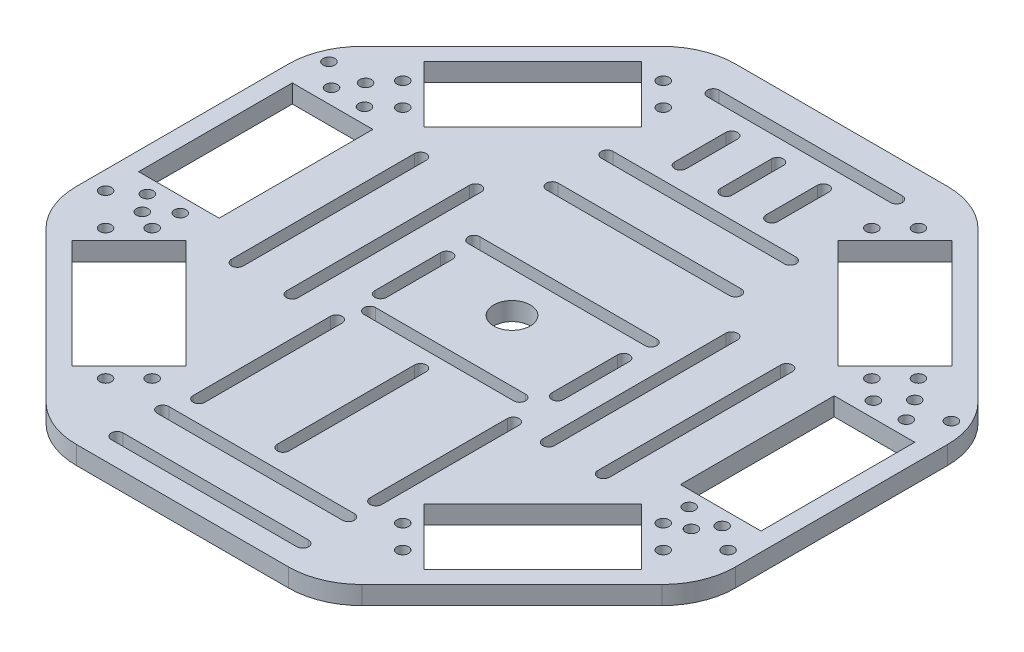
SolidWorks part; units mm, degrees
ref_plane "Front Plane" through (0, 0, 0) normal (0, 0, 1) x (1, 0, 0)
ref_plane "Top Plane" through (0, 0, 0) normal (0, 1, 0) x (1, 0, 0)
ref_plane "Right Plane" through (0, 0, 0) normal (1, 0, 0) x (0, 0, -1)
sketch "Sketch1" plane through (0, 0, 0) normal (0, 1, 0) x (1, 0, 0)
  line L1 (-90, -37.2792) -> (-37.2792, -90)
  line L2 (-37.2792, -90) -> (37.2792, -90)
  line L3 (37.2792, -90) -> (90, -37.2792)
  line L4 (90, -37.2792) -> (90, 37.2792)
  line L5 (90, 37.2792) -> (37.2792, 90)
  line L6 (37.2792, 90) -> (-37.2792, 90)
  line L7 (-37.2792, 90) -> (-90, 37.2792)
  line L8 (-90, 37.2792) -> (-90, -37.2792)
  line L12 (63.6396, -63.6396) -> (0, 0) construction
  line L21 (-20.4, -34.5422) -> (-34.5422, -20.4)
  line L22 (-20.4, -34.5422) -> (-50.0985, -64.2407)
  line L23 (-50.0985, -64.2407) -> (-64.2407, -50.0985)
  line L24 (-34.5422, -20.4) -> (-64.2407, -50.0985)
  line L25 (-38.85, -10) -> (-38.85, 10)
  line L26 (-38.85, -10) -> (-80.85, -10)
  line L27 (-80.85, -10) -> (-80.85, 10)
  line L28 (-38.85, 10) -> (-80.85, 10)
  line L29 (-34.5422, 20.4) -> (-20.4, 34.5422)
  line L30 (-34.5422, 20.4) -> (-64.2407, 50.0985)
  line L31 (-64.2407, 50.0985) -> (-50.0985, 64.2407)
  line L32 (-20.4, 34.5422) -> (-50.0985, 64.2407)
  line L37 (20.4, 34.5422) -> (34.5422, 20.4)
  line L38 (20.4, 34.5422) -> (50.0985, 64.2407)
  line L39 (50.0985, 64.2407) -> (64.2407, 50.0985)
  line L40 (34.5422, 20.4) -> (64.2407, 50.0985)
  line L41 (38.85, 10) -> (38.85, -10)
  line L42 (38.85, 10) -> (80.85, 10)
  line L43 (80.85, 10) -> (80.85, -10)
  line L44 (38.85, -10) -> (80.85, -10)
  circle A0 centre (0, 0) radius 90 construction
  circle A13 centre (0, 0) radius 90 construction
  circle A14 centre (-27.7186, -21.3546) radius 2.5
  circle A15 centre (-21.3546, -27.7186) radius 2.5
  circle A16 centre (-56.9221, -63.2861) radius 2.5
  circle A17 centre (-63.2861, -56.9221) radius 2.5
  circle A18 centre (0, 0) radius 90 construction
  circle A19 centre (-34.7, 4.5) radius 2.5
  circle A20 centre (-34.7, -4.5) radius 2.5
  circle A21 centre (-85, -4.5) radius 2.5
  circle A22 centre (-85, 4.5) radius 2.5
  circle A23 centre (0, 0) radius 90 construction
  circle A24 centre (-21.3546, 27.7186) radius 2.5
  circle A25 centre (-27.7186, 21.3546) radius 2.5
  circle A26 centre (-63.2861, 56.9221) radius 2.5
  circle A27 centre (-56.9221, 63.2861) radius 2.5
  circle A28 centre (0, 0) radius 90 construction
  circle A33 centre (0, 0) radius 90 construction
  circle A34 centre (27.7186, 21.3546) radius 2.5
  circle A35 centre (21.3546, 27.7186) radius 2.5
  circle A36 centre (56.9221, 63.2861) radius 2.5
  circle A37 centre (63.2861, 56.9221) radius 2.5
  circle A38 centre (0, 0) radius 90 construction
  circle A39 centre (34.7, -4.5) radius 2.5
  circle A40 centre (34.7, 4.5) radius 2.5
  circle A41 centre (85, 4.5) radius 2.5
  circle A42 centre (85, -4.5) radius 2.5
  circle A43 centre (0, 0) radius 90 construction
  point P15 (63.6396, -63.6396)
  point P16 (60.1041, -60.1041)
  point P17 (57.1696, -57.1696)
  point P121 (0, 0)
  dimension "D1" = 90
  dimension "D12" = 8
extrude "Baseplate" add sketch "Sketch1" along normal blind 5 contours L7 L8 L1 L2 L3 L4 L5 L6 A42 A41 A40 A39 A37 A36 A35 A34 A27 A26 A25 A24 A22 A21 A20 A19 A17 A16 A15 A14 L44 L41 | L29 L32 L31 L30 | L37 L40 L39 L38 | L41 L44 L43 L42 | L25 L28 L27 L26 | A27 | A26 | A25 | A24 | A22 | A21 | A19 | A20 | A14 | A15 | A17 | A16 | A40 | A41 | A42 | A35 | A34 | A39 | A37 | A36 | L21 L24 L23 L22 region at (1.7472, 0, 1.7472) region at (-59.85, 0, 0) region at (-42.3203, 0, -42.3203) region at (42.3203, 0, -42.3203) region at (59.85, 0, 0) region at (-27.7186, 0, 21.3546) region at (-21.3546, 0, 27.7186) region at (-56.9221, 0, 63.2861) region at (-63.2861, 0, 56.9221) region at (-34.7, 0, -4.5) region at (-34.7, 0, 4.5) region at (-85, 0, 4.5) region at (-85, 0, -4.5) region at (-21.3546, 0, -27.7186) region at (-27.7186, 0, -21.3546) region at (-63.2861, 0, -56.9221) region at (-56.9221, 0, -63.2861) region at (34.7, 0, -4.5) region at (85, 0, -4.5) region at (85, 0, 4.5)
fillet "Fillet1" radius 20 8 edges at (-90, 2.5, -37.2792) (-37.2792, 2.5, -90) (37.2792, 2.5, -90) (90, 2.5, -37.2792) (90, 2.5, 37.2792) (37.2792, 2.5, 90) (-37.2792, 2.5, 90) (-90, 2.5, 37.2792)
sketch "Sketch2" plane through (0, 5, 0) normal (0, 1, 0) x (1, 0, 0)
  line L0 (90, -28.9949) -> (90, 28.9949) construction
  line L1 (63, 25.0051) -> (85, 25.0051)
  line L2 (63, 25.0051) -> (63, -16.9949)
  line L3 (63, -16.9949) -> (85, -16.9949)
  line L4 (85, 25.0051) -> (85, -16.9949)
  circle A0 centre (78.5, 29.2051) radius 1.6
  circle A1 centre (69.5, 29.2051) radius 1.6
  circle A2 centre (69.5, -21.0949) radius 1.6
  circle A3 centre (78.5, -21.0949) radius 1.6
  point P8 (74, 25.0051)
  dimension "D1" = 3.2
  dimension "D2" = 9
  dimension "D3" = 50.3
  dimension "D4" = 22
  dimension "D5" = 42
  dimension "D6" = 4.2
  dimension "D7" = 4.5
  dimension "D8" = 5
  dimension "D9" = 12
extrude "Servo hole" cut sketch "Sketch2" against normal through all contours A0 | L4 L1 L2 L3 | A2 | A3 | A1 region at (74, 5, -4.0051) region at (78.5, 5, -29.2051) region at (69.5, 5, 21.0949) region at (78.5, 5, 21.0949)
sketch "Sketch3" plane through (0, 5, 0) normal (0, 1, 0) x (1, 0, 0)
  circle A0 centre (0, 0) radius 5
  dimension "D1" = 10
extrude "Center hole" cut sketch "Sketch3" against normal through all
pattern_circular "Servo hole pattern" count 8 over 360 about axis through (0, 5, 0) along (0, 1, 0) skipping 2, 3, 4, 5, 6 of "Servo hole"
sketch "Sketch4" plane through (0, 5, 0) normal (0, 1, 0) x (1, 0, 0)
  line L0 (-28.9949, -90) -> (28.9949, -90) construction
  line L1 (-90, 28.9949) -> (-90, -28.9949) construction
  circle A0 centre (-23, 5.1332) radius 1.6
  circle A1 centre (-23, -70) radius 1.6
  circle A2 centre (25.3362, 12.6262) radius 1.6
  circle A3 centre (25.3362, -70) radius 1.6
  circle A4 centre (-7.5585, -18.3745) radius 1.6
  circle A5 centre (20.4577, -18.3745) radius 1.6
  dimension "D1" = 3.2
  dimension "D8" = 20
  dimension "D2" = 7.493
  dimension "D3" = 48.3362
  dimension "D4" = 31.0007
  dimension "D5" = 51.6255
  dimension "D6" = 4.8785
  dimension "D7" = 28.0162
  dimension "D9" = 67
extrude "Arduino Screw holes" cut sketch "Sketch4" against normal through all
ref_plane "Midplane" through (0, 0, 0) normal (1, 0, 0) x (0, 0, -1)
mirror "Mirror1" about plane through (0, 0, 0) normal (1, 0, 0) of "Servo hole pattern", "Servo hole"
sketch "Sketch5" plane through (0, 5, 0) normal (0, 1, 0) x (1, 0, 0)
  line L0 (-25, 36) -> (25, 36) construction
  line L1 (-25, 37.6) -> (25, 37.6)
  line L2 (-25, 34.4) -> (25, 34.4)
  line L3 (-25, 51) -> (25, 51) construction
  line L4 (-25, 52.6) -> (25, 52.6)
  line L5 (-25, 49.4) -> (25, 49.4)
  line L6 (-50, 25) -> (-50, -25) construction
  line L7 (-48.4, 25) -> (-48.4, -25)
  line L8 (-51.6, 25) -> (-51.6, -25)
  line L9 (-35, 25) -> (-35, -25) construction
  line L10 (-33.4, 25) -> (-33.4, -25)
  line L11 (-36.6, 25) -> (-36.6, -25)
  line L12 (35, 25) -> (35, -25) construction
  line L13 (36.6, 25) -> (36.6, -25)
  line L14 (33.4, 25) -> (33.4, -25)
  line L15 (50, 25) -> (50, -25) construction
  line L16 (51.6, 25) -> (51.6, -25)
  line L17 (48.4, 25) -> (48.4, -25)
  line L18 (-25, 80) -> (25, 80) construction
  line L19 (-25, 81.6) -> (25, 81.6)
  line L20 (-25, 78.4) -> (25, 78.4)
  line L21 (-12.5, 72.5) -> (-12.5, 58.5) construction
  line L22 (-10.9, 72.5) -> (-10.9, 58.5)
  line L23 (-14.1, 72.5) -> (-14.1, 58.5)
  line L24 (12.5, 72.5) -> (12.5, 58.5) construction
  line L25 (14.1, 72.5) -> (14.1, 58.5)
  line L26 (10.9, 72.5) -> (10.9, 58.5)
  line L27 (28.9949, 90) -> (-28.9949, 90) construction
  line L28 (0, 72.5) -> (0, 58.5) construction
  line L29 (1.6, 72.5) -> (1.6, 58.5)
  line L30 (-1.6, 72.5) -> (-1.6, 58.5)
  arc A0 (-25, 37.6) -> (-25, 34.4) centre (-25, 36) ccw
  arc A1 (25, 34.4) -> (25, 37.6) centre (25, 36) ccw
  arc A2 (-25, 52.6) -> (-25, 49.4) centre (-25, 51) ccw
  arc A3 (25, 49.4) -> (25, 52.6) centre (25, 51) ccw
  arc A4 (-48.4, 25) -> (-51.6, 25) centre (-50, 25) ccw
  arc A5 (-51.6, -25) -> (-48.4, -25) centre (-50, -25) ccw
  arc A6 (-33.4, 25) -> (-36.6, 25) centre (-35, 25) ccw
  arc A7 (-36.6, -25) -> (-33.4, -25) centre (-35, -25) ccw
  arc A8 (36.6, 25) -> (33.4, 25) centre (35, 25) ccw
  arc A9 (33.4, -25) -> (36.6, -25) centre (35, -25) ccw
  arc A10 (51.6, 25) -> (48.4, 25) centre (50, 25) ccw
  arc A11 (48.4, -25) -> (51.6, -25) centre (50, -25) ccw
  arc A12 (-25, 81.6) -> (-25, 78.4) centre (-25, 80) ccw
  arc A13 (25, 78.4) -> (25, 81.6) centre (25, 80) ccw
  arc A14 (-10.9, 72.5) -> (-14.1, 72.5) centre (-12.5, 72.5) ccw
  arc A15 (-14.1, 58.5) -> (-10.9, 58.5) centre (-12.5, 58.5) ccw
  arc A16 (14.1, 72.5) -> (10.9, 72.5) centre (12.5, 72.5) ccw
  arc A17 (10.9, 58.5) -> (14.1, 58.5) centre (12.5, 58.5) ccw
  arc A18 (1.6, 72.5) -> (-1.6, 72.5) centre (0, 72.5) ccw
  arc A19 (-1.6, 58.5) -> (1.6, 58.5) centre (0, 58.5) ccw
  point P2 (0, 36)
  point P7 (0, 51)
  point P14 (-50, 0)
  point P21 (-35, 0)
  point P28 (35, 0)
  point P35 (50, 0)
  point P42 (0, 80)
  point P48 (-12.5, 65.5)
  point P57 (12.5, 65.5)
  point P64 (0, 65.5)
  dimension "D1" = 1.6
  dimension "D7" = 50
  dimension "D2" = 15
  dimension "D3" = 15
  dimension "D4" = 15
  dimension "D5" = 10
  dimension "D6" = 50
  dimension "D8" = 35
  dimension "D9" = 35
  dimension "D10" = 36
  dimension "D11" = 12.5
  dimension "D12" = 12.5
  dimension "D13" = 7.5
  dimension "D14" = 7.5
extrude "Slits" cut sketch "Sketch5" against normal through all contours L30 A19 L29 A18 | L26 A17 L25 A16 | L5 A3 L4 A2 | L2 A1 L1 A0 | L8 A5 L7 A4 | L11 A7 L10 A6 | L14 A9 L13 A8 | L17 A11 L16 A10 | L19 A13 L20 A12 | L22 A15 L23 A14 region at (0, 5, -36) region at (0, 5, -51) region at (-50, 5, 0) region at (-35, 5, 0) region at (35, 5, 0) region at (50, 5, 0) region at (12.5, 5, -65.5) region at (0, 5, -65.5)
sketch "Sketch6" plane through (0, 5, 0) normal (0, 1, 0) x (1, 0, 0)
  circle A0 centre (-75, 35) radius 1.6
  circle A1 centre (-85, 35) radius 1.6
  dimension "D1" = 3.2
  dimension "D3" = 10
  dimension "D4" = 85
  dimension "D5" = 35
extrude "Exterior Screw Holes" cut sketch "Sketch6" against normal through all
ref_plane "Plane1" through (0, 0, 0) normal (0, 0, 1) x (1, 0, 0)
mirror "Mirror2" about plane through (0, 0, 0) normal (1, 0, 0) of "Exterior Screw Holes"
sketch "Sketch7" plane through (0, 5, 0) normal (0, 1, 0) x (1, 0, 0)
  line L0 (-85, 35) -> (-85, 2.3324)
  circle A0 centre (-85, -26) radius 1.6
  circle A1 centre (-75, -26) radius 1.6
  dimension "D1" = 3.2
  dimension "D3" = 10
  dimension "D4" = 61
extrude "Cut-Extrude1" cut sketch "Sketch7" against normal through all contours A1 | A0 region at (-75, 5, 26)
mirror "Mirror3" about plane through (0, 0, 0) normal (1, 0, 0) of "Cut-Extrude1"
sketch "Sketch8" plane through (0, 5, 0) normal (0, 1, 0) x (1, 0, 0)
  line L0 (20.4577, -18.3745) -> (-20.4577, -18.3745) construction
  line L1 (20.4577, -19.9745) -> (-20.4577, -19.9745)
  line L2 (20.4577, -16.7745) -> (-20.4577, -16.7745)
  line L3 (0, -25.4762) -> (0, 25.4762) construction
  line L4 (25.3362, 12.6262) -> (-23, 12.6262) construction
  line L5 (25.3362, 11.0262) -> (-23, 11.0262)
  line L6 (25.3362, 14.2262) -> (-23, 14.2262)
  line L7 (-23, -12.8668) -> (-23, 5.1332) construction
  line L8 (-24.6, -12.8668) -> (-24.6, 5.1332)
  line L9 (-21.4, -12.8668) -> (-21.4, 5.1332)
  line L10 (25.3362, 5.1332) -> (25.3362, -12.8668) construction
  line L11 (26.9362, 5.1332) -> (26.9362, -12.8668)
  line L12 (23.7362, 5.1332) -> (23.7362, -12.8668)
  line L13 (-25.3362, -70) -> (25.3362, -70) construction
  line L14 (-25.3362, -68.4) -> (25.3362, -68.4)
  line L15 (-25.3362, -71.6) -> (25.3362, -71.6)
  line L16 (-23, -25) -> (-23, -62.5) construction
  line L17 (-21.4, -25) -> (-21.4, -62.5)
  line L18 (-24.6, -25) -> (-24.6, -62.5)
  line L19 (25.3362, -62.5) -> (25.3362, -25) construction
  line L20 (23.7362, -62.5) -> (23.7362, -25)
  line L21 (26.9362, -62.5) -> (26.9362, -25)
  line L22 (0, -62.5) -> (0, -25) construction
  line L23 (-1.6, -62.5) -> (-1.6, -25)
  line L24 (1.6, -62.5) -> (1.6, -25)
  line L25 (-25.3362, -82.5) -> (25.3362, -82.5) construction
  line L26 (-25.3362, -80.9) -> (25.3362, -80.9)
  line L27 (-25.3362, -84.1) -> (25.3362, -84.1)
  arc A0 (20.4577, -19.9745) -> (20.4577, -16.7745) centre (20.4577, -18.3745) ccw
  arc A1 (-20.4577, -16.7745) -> (-20.4577, -19.9745) centre (-20.4577, -18.3745) ccw
  circle A2 centre (-7.5585, -18.3745) radius 1.6 construction
  arc A3 (25.3362, 11.0262) -> (25.3362, 14.2262) centre (25.3362, 12.6262) ccw
  arc A4 (-23, 14.2262) -> (-23, 11.0262) centre (-23, 12.6262) ccw
  arc A5 (-24.6, -12.8668) -> (-21.4, -12.8668) centre (-23, -12.8668) ccw
  arc A6 (-21.4, 5.1332) -> (-24.6, 5.1332) centre (-23, 5.1332) ccw
  arc A7 (26.9362, 5.1332) -> (23.7362, 5.1332) centre (25.3362, 5.1332) ccw
  arc A8 (23.7362, -12.8668) -> (26.9362, -12.8668) centre (25.3362, -12.8668) ccw
  arc A9 (-25.3362, -68.4) -> (-25.3362, -71.6) centre (-25.3362, -70) ccw
  arc A10 (25.3362, -71.6) -> (25.3362, -68.4) centre (25.3362, -70) ccw
  arc A11 (-21.4, -25) -> (-24.6, -25) centre (-23, -25) ccw
  arc A12 (-24.6, -62.5) -> (-21.4, -62.5) centre (-23, -62.5) ccw
  arc A13 (23.7362, -62.5) -> (26.9362, -62.5) centre (25.3362, -62.5) ccw
  arc A14 (26.9362, -25) -> (23.7362, -25) centre (25.3362, -25) ccw
  arc A15 (-1.6, -62.5) -> (1.6, -62.5) centre (0, -62.5) ccw
  arc A16 (1.6, -25) -> (-1.6, -25) centre (0, -25) ccw
  arc A17 (-25.3362, -80.9) -> (-25.3362, -84.1) centre (-25.3362, -82.5) ccw
  arc A18 (25.3362, -84.1) -> (25.3362, -80.9) centre (25.3362, -82.5) ccw
  point P3 (0, -18.3745)
  point P8 (1.1681, 12.6262)
  point P20 (-23, -3.8668)
  point P30 (25.3362, -3.8668)
  point P35 (0, -70)
  point P40 (-23, -43.75)
  point P50 (25.3362, -43.75)
  point P57 (0, -43.75)
  point P65 (0, -82.5)
  dimension "D2" = 1.6
  dimension "D1" = 18
  dimension "D3" = 37.5
  dimension "D4" = 7.5
  dimension "D5" = 12.5
extrude "Cut-Extrude2" cut sketch "Sketch8" against normal through all contours L9 A6 L8 A5 | L12 A8 L11 A7 | L2 A1 L1 A0 | L24 A16 L23 A15 | L21 A14 L20 A13 | L27 A18 L26 A17 | L6 A4 L5 A3 | L17 A12 L18 A11 | L14 A10 L15 A9 region at (0, 5, 18.3745) region at (-23, 5, 3.8668) region at (25.3362, 5, 3.8668) region at (25.3362, 5, 43.75) region at (0, 5, 43.75) region at (0, 5, 82.5)
